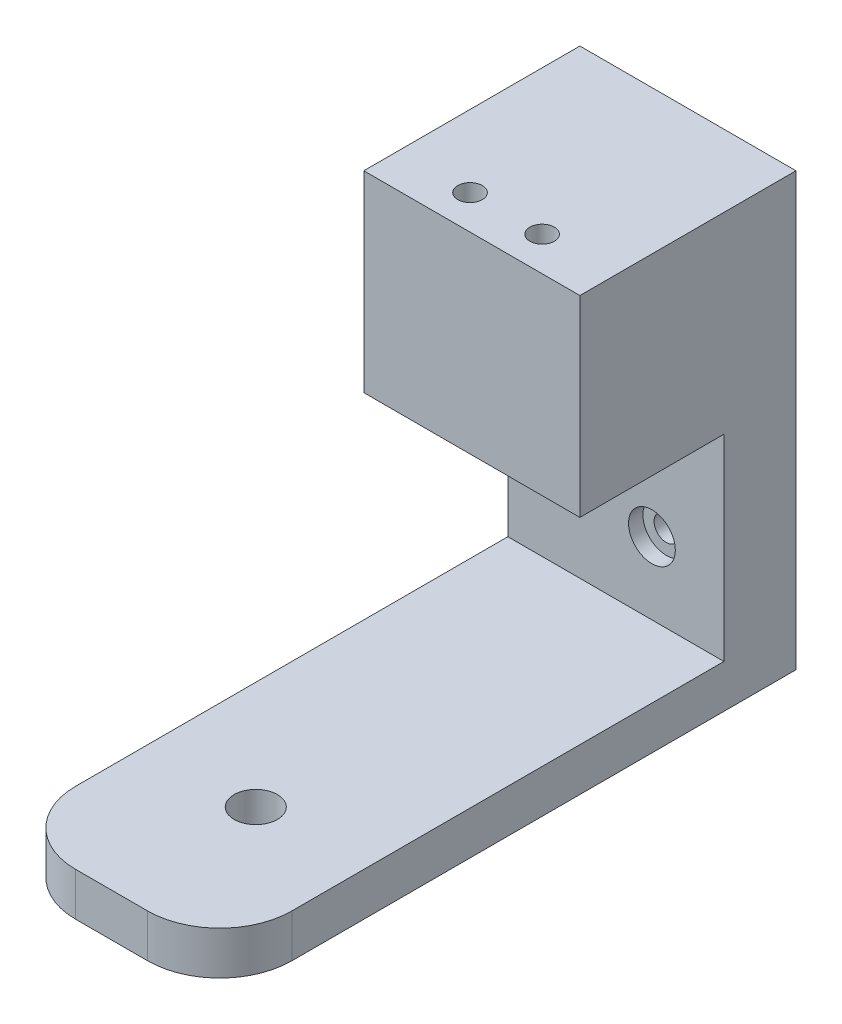
SolidWorks part; units mm, degrees
ref_plane "Plan de face" through (0, 0, 0) normal (0, 0, 1) x (1, 0, 0)
ref_plane "Plan de dessus" through (0, 0, 0) normal (0, 1, 0) x (1, 0, 0)
ref_plane "Plan de droite" through (0, 0, 0) normal (1, 0, 0) x (0, 0, -1)
sketch "Esquisse1" plane through (0, 0, 0) normal (0, 0, 1) x (1, 0, 0)
  line L1 (0, 0) -> (30, 0)
  line L2 (0, 0) -> (0, 60)
  line L3 (0, 60) -> (30, 60)
  line L4 (30, 0) -> (30, 60)
  dimension "D1" = 30
  dimension "D2" = 60
extrude "Boss.-Extru.1" add sketch "Esquisse1" along normal blind 10
sketch "Esquisse2" plane through (0, 0, 10) normal (0, 0, 1) x (1, 0, 0)
  line L0 (30, 0) -> (30, 60) construction
  line L1 (0, 0) -> (30, 0) construction
  line L2 (0, 60) -> (0, 0) construction
  line L3 (30, 0) -> (30, 6)
  line L4 (0, 0) -> (30, 0)
  line L5 (0, 6) -> (0, 0)
  line L6 (0, 6) -> (30, 6)
  dimension "D1" = 6
extrude "Boss.-Extru.2" add sketch "Esquisse2" along normal blind 70
sketch "Esquisse3" plane through (0, 0, 0) normal (0, -1, 0) x (1, 0, 0)
  line L0 (0, 80) -> (0, 0) construction
  line L1 (0, 0) -> (30, 0) construction
  circle A0 centre (15, 60) radius 3
  dimension "D3" = 6
  dimension "D1" = 15
  dimension "D2" = 60
extrude "Enlèv. mat.-Extru.1" cut sketch "Esquisse3" against normal up to surface (6 mm away) up to face at (15, 6, 45)
sketch "Esquisse4" plane through (0, 0, 10) normal (0, 0, 1) x (1, 0, 0)
  line L0 (30, 6) -> (30, 60) construction
  line L1 (30, 33.32) -> (30, 60)
  line L2 (0, 60) -> (0, 6) construction
  line L3 (30, 60) -> (0, 60) construction
  line L4 (0, 60) -> (0, 33.32)
  line L5 (30, 60) -> (0, 60)
  line L6 (0, 33.32) -> (30, 33.32)
  dimension "D1" = 26.68
extrude "Boss.-Extru.3" add sketch "Esquisse4" along normal blind 20
sketch "Esquisse5" plane through (0, 33.32, 0) normal (0, -1, 0) x (1, 0, 0)
  line L0 (0, 30) -> (0, 10) construction
  line L2 (0, 30) -> (30, 30) construction
  circle A0 centre (10, 25.25) radius 2.2
  circle A1 centre (20, 25.25) radius 2.2
  dimension "D3" = 4.4
  dimension "D4" = 4.4
  dimension "D1" = 10
  dimension "D2" = 10
  dimension "D5" = 4.75
  dimension "D6" = 4.75
hole_wizard "Dégagement M31" positions "Esquisse8" profile "Esquisse7" hole size "M3" standard "ISO"
sketch "Esquisse8" plane through (0, 33.32, 0) normal (0, -1, 0) x (-1, 0, 0)
  point P0 (-10, -25.25)
  point P3 (-20, -25.25)
sketch "Esquisse7" plane through (10, 33.32, 25.25) normal (1, 0, 0) x (0, 0, -1)
  line L0 (0, 0) -> (0, 27.7015)
  line L1 (0, 27.7015) -> (1.7, 26.68)
  line L2 (1.7, 26.68) -> (1.7, 0)
  line L5 (1.7, 0) -> (0, 0)
  line L10 (0, 27.7015) -> (-1.7, 26.68) construction
  line L11 (0, -6.35) -> (0, 107.95) construction
  dimension "Diamètre du perçage" = 3.4
  dimension "Profondeur du perçage" = 26.68
  dimension "Angle de pointe" = 118
sketch "Esquisse9" plane through (0, 0, 10) normal (0, 0, 1) x (1, 0, 0)
  line L0 (0, 33.32) -> (0, 6) construction
  line L1 (30, 6) -> (30, 33.32) construction
  line L2 (30, 6) -> (0, 6) construction
  line L3 (0, 33.32) -> (30, 33.32) construction
  circle A1 centre (20, 16) radius 1.5
  circle A2 centre (10, 23.32) radius 1.5
  dimension "D2" = 3
  dimension "D4" = 3
  dimension "D1" = 10
  dimension "D3" = 10
  dimension "D5" = 10
  dimension "D6" = 10
hole_wizard "Chambrage pour tête cylindrique fendue M31" positions "Esquisse10" profile "Esquisse12" counterbore size "M3" standard "ISO"
sketch "Esquisse10" plane through (0, 0, 10) normal (0, 0, 1) x (1, 0, 0)
  point P0 (10, 23.32)
  point P3 (20, 16)
sketch "Esquisse12" plane through (10, 23.32, 10) normal (1, 0, 0) x (0, -1, 0)
  line L0 (0, 0) -> (0, 11.0215)
  line L1 (0, 11.0215) -> (1.7, 10)
  line L2 (1.7, 10) -> (1.7, 2)
  line L3 (1.7, 2) -> (3.25, 2)
  line L4 (3.25, 2) -> (3.25, 0)
  line L5 (3.25, 0) -> (0, 0)
  line L10 (0, 11.0215) -> (-1.7, 10) construction
  line L11 (0, -6.35) -> (0, 107.95) construction
  dimension "Diamètre du perçage" = 3.4
  dimension "Profondeur du perçage" = 10
  dimension "Diamètre du chambrage" = 6.5
  dimension "Profondeur du chambrage" = 2
  dimension "Angle de pointe" = 118
fillet "Congé1" radius 10 2 edges at (30, 3, 80) (0, 3, 80)
equation "\"D4@Esquisse5\"=\"D3@Esquisse5\""
equation "\"D6@Esquisse5\"=\"D5@Esquisse5\""
